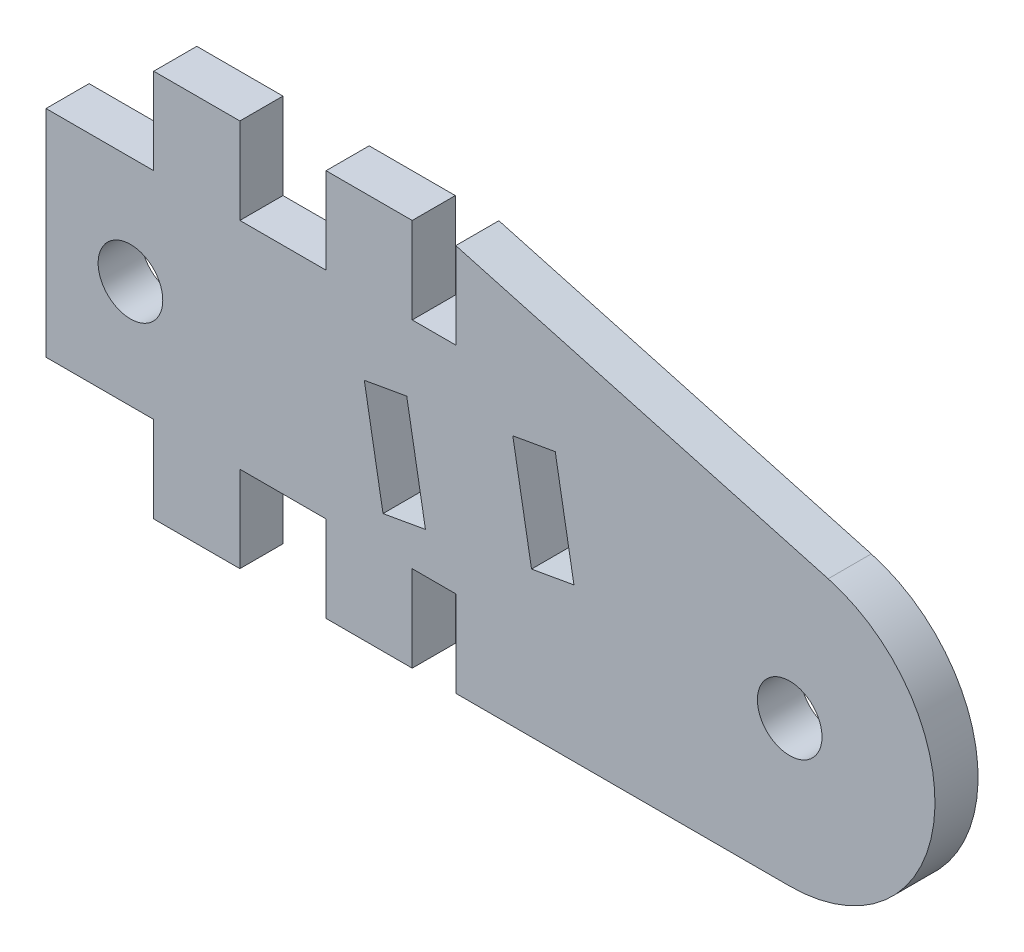
SolidWorks part; units mm, degrees
ref_plane "Front Plane" through (0, 0, 0) normal (0, 0, 1) x (1, 0, 0)
ref_plane "Top Plane" through (0, 0, 0) normal (0, 1, 0) x (1, 0, 0)
ref_plane "Right Plane" through (0, 0, 0) normal (1, 0, 0) x (0, 0, -1)
sketch "Sketch1" plane through (0, 0, 0) normal (0, 0, 1) x (1, 0, 0)
  line L0 (3.92, 0) -> (7.92, 0)
  line L1 (3.92, 4) -> (3.92, 0)
  line L2 (3.92, 14) -> (-1.08, 14)
  line L3 (7.92, 4) -> (11.92, 4)
  line L4 (11.92, 4) -> (11.92, 0)
  line L5 (7.92, 0) -> (7.92, 4)
  line L6 (11.92, 0) -> (15.92, 0)
  line L7 (15.92, 0) -> (15.92, 4)
  line L8 (15.92, 4) -> (17.9415, 4)
  line L9 (-1.08, 14) -> (-1.08, 4)
  line L10 (17.9415, 4) -> (17.9415, 0)
  line L11 (15.92, 14) -> (17.9416, 14)
  line L12 (15.92, 18) -> (15.92, 14)
  line L13 (11.92, 18) -> (15.92, 18)
  line L14 (7.92, 18) -> (7.92, 14)
  line L15 (11.92, 14) -> (11.92, 18)
  line L16 (7.92, 14) -> (11.92, 14)
  line L17 (-1.08, 4) -> (3.92, 4)
  line L18 (3.92, 14) -> (3.92, 18)
  line L19 (3.92, 18) -> (7.92, 18)
  line L20 (17.9415, 0) -> (33.4415, 0)
  line L22 (17.9416, 14) -> (17.9416, 18)
  line L23 (17.9416, 18) -> (35.2288, 13.2496)
  line L27 (22.5591, 12.0249) -> (20.5895, 11.6776)
  line L32 (15.6655, 10.8093) -> (16.5337, 5.8853)
  line L33 (15.6655, 10.8093) -> (13.6959, 10.462)
  line L34 (13.6959, 10.462) -> (14.5641, 5.538)
  line L35 (14.5641, 5.538) -> (16.5337, 5.8853)
  line L36 (20.5895, 11.6776) -> (21.4578, 6.7535)
  line L37 (21.4578, 6.7535) -> (23.4274, 7.1008)
  line L38 (22.5591, 12.0249) -> (23.4274, 7.1008)
  arc A0 (33.4415, 0) -> (35.2288, 13.2496) centre (33.4415, 6.7453) ccw
  circle A1 centre (2.8405, 9) radius 1.5
  circle A4 centre (33.4415, 6.7453) radius 1.5
  dimension "D16" = 6.7453
  dimension "D19" = 3
  dimension "D21" = 3
  dimension "D3" = 4
  dimension "D4" = 4
  dimension "D5" = 4
  dimension "D6" = 4
  dimension "D7" = 2.0215
  dimension "D8" = 10
  dimension "D9" = 5
  dimension "D10" = 4
  dimension "D11" = 4
  dimension "D12" = 4
  dimension "D14" = 15.5
  dimension "D15" = 4
  dimension "D20" = 4
  dimension "D24" = 5
  dimension "D25" = 5
extrude "Boss-Extrude1" add sketch "Sketch1" along normal blind 2
